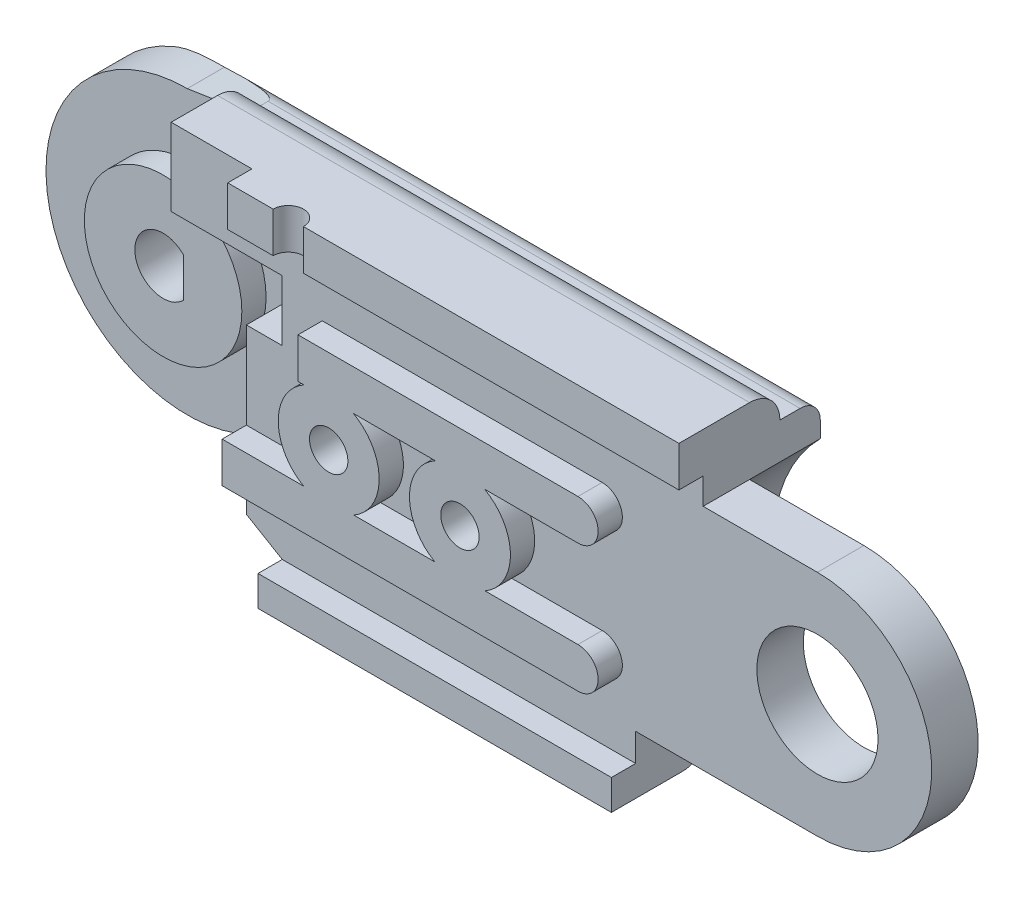
SolidWorks part; units mm, degrees
ref_plane "Front Plane" through (0, 0, 0) normal (0, 0, 1) x (1, 0, 0)
ref_plane "Top Plane" through (0, 0, 0) normal (0, 1, 0) x (1, 0, 0)
ref_plane "Right Plane" through (0, 0, 0) normal (1, 0, 0) x (0, 0, -1)
sketch "Sketch2" plane through (0, 0, 0) normal (0, 0, 1) x (1, 0, 0)
  line L0 (0, 0) -> (35, 0) construction
  line L1 (0, 19.5448) -> (0, -26.0212) construction
  line L2 (0, 7) -> (3, 7.4569)
  line L3 (3, 7.4569) -> (29.3431, 7.4569)
  line L4 (29.3431, 5.6569) -> (29.3431, 7.4569)
  line L5 (29.3431, 5.6569) -> (35, 0) construction
  line L6 (27, 0) -> (26, -2.5431)
  line L7 (26, -2.5431) -> (26, -7.0431)
  line L8 (26, -7.0431) -> (8.4997, -7.0431)
  line L9 (0, 0) -> (4.9497, -4.9497) construction
  line L10 (4.9497, -4.9497) -> (8.4997, -7.0431)
  arc A0 (0, 7) -> (4.9497, -4.9497) centre (0, 0) ccw
  arc A2 (29.3431, 5.6569) -> (27, 0) centre (35, 0) ccw
  dimension "D1" = 3
  dimension "D2" = 14
  dimension "D5" = 45
  dimension "D6" = 16
  dimension "D3" = 1.8
  dimension "D4" = 35
  dimension "D7" = 1
  dimension "D8" = 4.5
  dimension "D9" = 45
  dimension "D10" = 3.55
  dimension "D11" = 14.5
  dimension "D12" = 2.5431
extrude "Boss-Extrude1" add sketch "Sketch2" along normal blind 2
sketch "Sketch3" plane through (0, 0, 2) normal (0, 0, 1) x (1, 0, 0)
  line L0 (29.3431, 7.4569) -> (29.3431, 5.6569)
  line L1 (27, 0) -> (26, -2.5431)
  line L2 (26, -2.5431) -> (27, 0) construction
  line L3 (26, -2.5431) -> (26, -7.0431)
  line L5 (8.4997, -7.0431) -> (6.7247, -5.9964)
  line L6 (4.9497, -4.9497) -> (8.4997, -7.0431) construction
  line L8 (3, 7.4569) -> (3, 2.1269)
  line L9 (3, 2.1269) -> (6.7247, 2.1269)
  line L10 (6.7247, 2.1269) -> (6.7247, -5.9964)
  line L11 (3, 7.4569) -> (3, 8.9569)
  line L12 (3, 8.9569) -> (29.3431, 8.9569)
  line L13 (29.3431, 8.9569) -> (29.3431, 7.4569)
  line L14 (8.4997, -7.0431) -> (8.4997, -8.5431)
  line L15 (8.4997, -8.5431) -> (26, -8.5431)
  line L16 (26, -8.5431) -> (26, -7.0431)
  line L17 (29.3431, 7.4569) -> (3, 7.4569) construction
  arc A0 (29.3431, 5.6569) -> (27, 0) centre (35, 0) ccw
  arc A1 (29.3431, 5.6569) -> (27, 0) centre (35, 0) ccw construction
  dimension "D1" = 5.33
  dimension "D2" = 1.5
  dimension "D3" = 1.5
extrude "Boss-Extrude2" add sketch "Sketch3" along normal blind 1.5
ref_plane "Plane1" through (0, 0, 3.5) normal (0, 0, 1) x (1, 0, 0)
sketch "Sketch5" plane through (0, 0, 3.5) normal (0, 0, 1) x (1, 0, 0)
  line L0 (3, 7.5) -> (3, 2.1269)
  line L1 (3, 2.1269) -> (6.7247, 2.1269)
  line L2 (6.7247, 2.1269) -> (6.7247, -5.9964)
  line L4 (8.4997, -8.5431) -> (26, -8.5431)
  line L6 (29.3431, 7.5) -> (29.3431, 5.6569)
  line L7 (29.3431, 5.6569) -> (35.0031, 5.6569)
  line L8 (35.0031, -5.6631) -> (26, -5.6631)
  line L9 (26, -8.5431) -> (26, -2.5431) construction
  line L10 (26, -5.6631) -> (26, -8.5431)
  line L11 (3, 7.5) -> (3, 8.9569)
  line L12 (3, 8.9569) -> (29.3431, 8.9569)
  line L13 (29.3431, 8.9569) -> (29.3431, 7.5)
  line L14 (6.7247, -5.9964) -> (8.4997, -7.0431)
  line L15 (8.4997, -7.0431) -> (8.4997, -8.5431)
  arc A0 (35.0031, -5.6631) -> (35.0031, 5.6569) centre (35.0031, -0.0031) ccw
  dimension "D2" = 5.66
  dimension "D1" = 5.66
extrude "Boss-Extrude3" add sketch "Sketch5" along normal blind 2.3 contours A0 L7 L6 L13 L12 L11 L0 L1 L2 L14 L15 L4 L10 L8
sketch "Sketch6" plane through (0, 0, 5.8) normal (0, 0, 1) x (1, 0, 0)
  line L0 (3, 2.1269) -> (3, 5.1269)
  line L1 (3, 2.1269) -> (8.48, 2.1269)
  line L2 (3, 5.1269) -> (8.48, 5.1269)
  line L3 (8.48, 2.1269) -> (8.48, 5.1269)
  line L4 (3, 8.9569) -> (3, 2.1269) construction
  dimension "D1" = 3
  dimension "D2" = 5.48
extrude "Cut-Extrude1" cut sketch "Sketch6" against normal blind 3.8
sketch "Sketch7" plane through (0, 0, 5.8) normal (0, 0, 1) x (1, 0, 0)
  circle A0 centre (35.0031, -0.0031) radius 3
  dimension "D1" = 6
extrude "Cut-Extrude2" cut sketch "Sketch7" against normal blind 3.3
sketch "Sketch8" plane through (0, 0, 5.8) normal (0, 0, 1) x (1, 0, 0)
  line L0 (29.3431, 8.9569) -> (7, 8.9569)
  line L1 (8.4997, -8.5431) -> (26, -8.5431) construction
  line L2 (7, 8.9569) -> (7, 6.9569)
  line L3 (7, 6.9569) -> (29.3431, 6.9569)
  line L4 (29.3431, 8.9569) -> (29.3431, 5.6569) construction
  line L5 (29.3431, 6.9569) -> (29.3431, 8.9569)
  line L6 (26, -8.5431) -> (26, -7.0431)
  line L7 (26, -8.5431) -> (8.4997, -8.5431)
  line L8 (8.4997, -8.5431) -> (8.4997, -7.0431)
  line L9 (8.4997, -7.0431) -> (26, -7.0431)
  line L10 (6.7247, -4.1697) -> (24.3431, -4.1697)
  line L11 (6.7247, 2.1269) -> (6.7247, -5.9964) construction
  line L12 (6.7247, -2.1697) -> (6.7247, -4.1697)
  line L13 (3, 8.9569) -> (29.3431, 8.9569) construction
  line L14 (3, 8.9569) -> (3, 5.1269) construction
  line L15 (24.3431, -2.1697) -> (6.7247, -2.1697)
  line L16 (24.3431, 4.1803) -> (10.48, 4.1803)
  line L17 (10.48, 4.1803) -> (10.48, 2.1803)
  line L18 (10.48, 2.1803) -> (24.3431, 2.1803)
  line L20 (26, -5.6631) -> (26, -8.5431) construction
  line L28 (8.48, 2.1269) -> (8.48, 5.1269) construction
  arc A0 (24.3431, -4.1697) -> (24.3431, -2.1697) centre (24.3431, -3.1697) ccw
  arc A1 (24.3431, 2.1803) -> (24.3431, 4.1803) centre (24.3431, 3.1803) ccw
  dimension "D2" = 1
  dimension "D5" = 5
  dimension "D7" = 1
  dimension "D1" = 2
  dimension "D3" = 2
  dimension "D4" = 2
  dimension "D6" = 5
  dimension "D8" = 4.35
  dimension "D9" = 4
extrude "Boss-Extrude4" add sketch "Sketch8" along normal blind 1.2
sketch "Sketch9" plane through (0, 0, 5.8) normal (0, 0, 1) x (1, 0, 0)
  line L0 (26, -8.5431) -> (26, -7.0431) construction
  circle A0 centre (18.5, 0) radius 2.5
  circle A1 centre (12, 0) radius 2.5
  dimension "D3" = 5
  dimension "D4" = 5
  dimension "D1" = 6.5
  dimension "D2" = 7.5
extrude "Boss-Extrude5" add sketch "Sketch9" along normal blind 1.2
sketch "Sketch10" plane through (0, 0, 7) normal (0, 0, 1) x (1, 0, 0)
  circle A0 centre (18.5, 0) radius 0.95
  circle A1 centre (12, 0) radius 0.95
extrude "Cut-Extrude3" cut sketch "Sketch10" against normal blind 8.2
sketch "Sketch11" plane through (0, 0, 0) normal (0, 0, -1) x (-1, 0, 0)
  circle A0 centre (-12, 0) radius 2
  circle A1 centre (-18.5, 0) radius 2
extrude "Cut-Extrude4" cut sketch "Sketch11" against normal blind 2.2
sketch "Sketch12" plane through (0, 0, 2) normal (0, 0, 1) x (1, 0, 0)
  circle A0 centre (0, 0) radius 3.9
extrude "Boss-Extrude6" add sketch "Sketch12" along normal blind 1.2
sketch "Sketch14" plane through (0, 0, 3.2) normal (0, 0, 1) x (1, 0, 0)
  line L0 (1, 0.9798) -> (1, -0.9798)
  arc A0 (1, 0.9798) -> (1, -0.9798) centre (0, 0) ccw
  dimension "D1" = 2.8
  dimension "D2" = 1
extrude "Cut-Extrude5" cut sketch "Sketch14" against normal blind 3.2 contours A0 L0
fillet "Fillet1" radius 1.5 2 edges at (16.1716, 8.9569, 2) (17.2499, -8.5431, 2)
fillet "Fillet2" radius 1 2 edges at (17.2499, -7.0431, 0) (16.1716, 7.4569, 0)
sketch "Sketch15" plane through (0, 6.9569, 0) normal (0, -1, 0) x (1, 0, 0)
  line L0 (7, 7) -> (29.3431, 7) construction
  line L1 (7, 7) -> (7, 5.8) construction
  circle A0 centre (10, 7) radius 0.75
  dimension "D1" = 3
  dimension "D2" = 1.5
extrude "Cut-Extrude6" cut sketch "Sketch15" against normal blind 10
